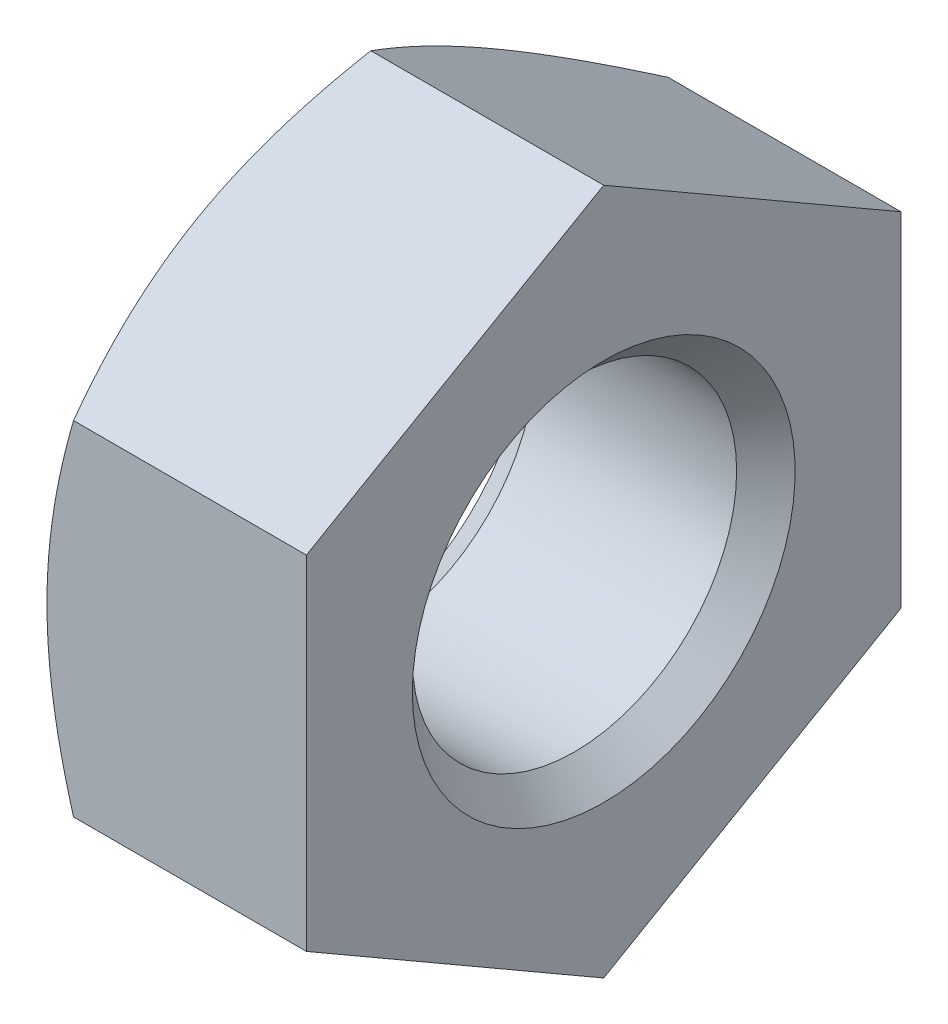
SolidWorks part; units mm, degrees
material "AISI 304"
ref_plane "正面" through (0, 0, 0) normal (0, 0, 1) x (1, 0, 0)
ref_plane "平面" through (0, 0, 0) normal (0, 1, 0) x (1, 0, 0)
ref_plane "右側面" through (0, 0, 0) normal (1, 0, 0) x (0, 0, -1)
ref_plane "Plane1" through (0, 0, 0) normal (0, 0, 1) x (1, 0, 0)
sketch "Sketch1" plane through (0, 0, 0) normal (0, 0, 1) x (1, 0, 0)
  line L0 (-1.2, 0) -> (-1.2, 2.75)
  line L1 (-1.2, 2.75) -> (-0.9402, 3.2)
  line L2 (-0.9402, 3.2) -> (1.2, 3.2)
  line L3 (1.2, 3.2) -> (1.2, 0)
  line L4 (1.2, 0) -> (-1.2, 0)
  line L5 (1.2, 0) -> (-1.2, 0) construction
revolve "Revolve1" add sketch "Sketch1" angle 360 about L5 reverse direction yes
ref_plane "Plane2" through (0, 0, 0) normal (0, 0, 1) x (1, 0, 0)
sketch "Sketch2" plane through (0, 0, 0) normal (0, 0, 1) x (1, 0, 0)
  line L0 (-1.2, 0) -> (-1.2, 1.7)
  line L1 (-1.2, 1.7) -> (-0.9295, 1.5)
  line L2 (-0.9295, 1.5) -> (0.9295, 1.5)
  line L3 (0.9295, 1.5) -> (1.2, 1.7705)
  line L4 (1.2, 1.7705) -> (1.2, 0)
  line L5 (1.2, 0) -> (-1.2, 0)
  line L6 (1.2, 0) -> (-1.2, 0) construction
  dimension "D1" = 1.5
  dimension "D2" = 1.7
revolve "Cut-Revolve1" cut sketch "Sketch2" angle 360 about L6 reverse direction yes
ref_plane "Plane3" through (0, 0, 0) normal (1, 0, 0) x (0, 0, -1)
sketch "Sketch3" plane through (0, 0, 0) normal (1, 0, 0) x (0, 0, -1)
  line L0 (-5.5, -5.5) -> (5.5, -5.5)
  line L1 (5.5, -5.5) -> (5.5, 5.5)
  line L2 (5.5, 5.5) -> (-5.5, 5.5)
  line L3 (-5.5, 5.5) -> (-5.5, -5.5)
  line L4 (-2.75, -1.5877) -> (0, -3.1754)
  line L5 (0, -3.1754) -> (2.75, -1.5877)
  line L6 (2.75, -1.5877) -> (2.75, 1.5877)
  line L7 (2.75, 1.5877) -> (0, 3.1754)
  line L8 (0, 3.1754) -> (-2.75, 1.5877)
  line L9 (-2.75, 1.5877) -> (-2.75, -1.5877)
extrude "Cut-Extrude1" cut sketch "Sketch3" against normal blind 1.2 and the other way blind 1.2
